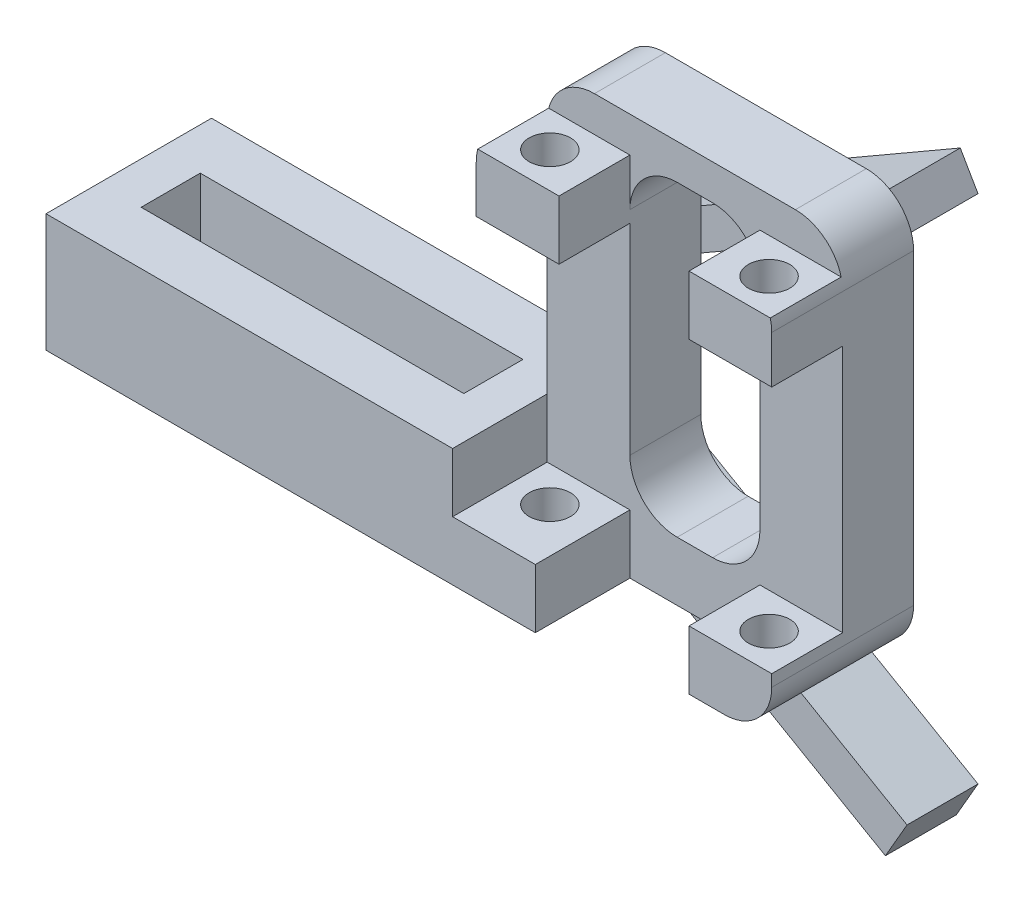
SolidWorks part; units mm, degrees
ref_plane "Alzado" through (0, 0, 0) normal (0, 0, 1) x (1, 0, 0)
ref_plane "Planta" through (0, 0, 0) normal (0, 1, 0) x (1, 0, 0)
ref_plane "Vista lateral" through (0, 0, 0) normal (1, 0, 0) x (0, 0, -1)
sketch "Croquis1" plane through (0, 0, 0) normal (0, 0, 1) x (1, 0, 0)
  line L1 (0, 0) -> (-25, 0)
  line L2 (0, 0) -> (0, -34)
  line L3 (0, -34) -> (-25, -34)
  line L4 (-25, 0) -> (-25, -34)
  dimension "D1" = 34
  dimension "D2" = 25
extrude "Saliente-Extruir1" add sketch "Croquis1" along normal blind 6
sketch "Croquis2" plane through (0, 0, 6) normal (0, 0, 1) x (1, 0, 0)
  line L0 (-25, 0) -> (-25, -34) construction
  line L1 (-25, -3) -> (-18, -3)
  line L2 (-25, -3) -> (-25, -8)
  line L3 (-25, -8) -> (-18, -8)
  line L4 (-18, -3) -> (-18, -8)
  line L5 (-12.5, 0) -> (-12.5, -3.7479) construction
  line L6 (0, 0) -> (-25, 0) construction
  line L7 (0, -8) -> (-7, -8)
  line L8 (-25, -34) -> (0, -34) construction
  line L9 (0, -34) -> (0, -29)
  line L10 (-7, -3) -> (-7, -8)
  line L11 (-18, 0) -> (-18, -3) construction
  line L12 (0, -3) -> (-7, -3)
  line L13 (0, -3) -> (0, -8)
  line L14 (-25, -29) -> (-18, -29)
  line L15 (-18, -34) -> (-18, -29)
  line L16 (-25, -34) -> (-18, -34)
  line L17 (-25, -34) -> (-25, -29)
  line L18 (0, -34) -> (-7, -34)
  line L19 (-7, -34) -> (-7, -29)
  line L20 (0, -29) -> (-7, -29)
  dimension "D1" = 5
  dimension "D2" = 3
  dimension "D3" = 7
  dimension "D4" = 7
  dimension "D5" = 5
extrude "Saliente-Extruir2" add sketch "Croquis2" along normal blind 6
sketch "Croquis3" plane through (0, 0, 6) normal (0, 0, 1) x (1, 0, 0)
  line L1 (-18, -3) -> (-7, -3)
  line L2 (-18, -3) -> (-18, -29)
  line L3 (-18, -29) -> (-7, -29)
  line L4 (-7, -3) -> (-7, -29)
extrude "Cortar-Extruir1" cut sketch "Croquis3" against normal up to next
fillet "Redondeo1" radius 4 8 edges at (-18, -29, 3) (-7, -29, 3) (-7, -3, 3) (-18, -3, 3) (0, 0, 3) (0, -34, 6) (-25, -34, 6) (-25, 0, 3)
sketch "Croquis5" plane through (0, 0, 0) normal (0, 0, -1) x (-1, 0, 0)
  line L0 (25, -29) -> (25, -30)
  line L1 (25, -34) -> (25, -36.4781) construction
  line L2 (25, -34) -> (59.4, -34)
  line L6 (25, -36.4781) -> (59.4, -36.4781) construction
  line L7 (25, -34) -> (21, -34)
  line L8 (25, -29) -> (25, -24)
  line L9 (25, -4) -> (25, -30) construction
  line L10 (25, -24) -> (59.4, -24)
  line L11 (59.4, -24) -> (59.4, -34)
  arc A1 (21, -34) -> (25, -30) centre (21, -30) ccw construction
  arc A2 (21, -34) -> (25, -30) centre (21, -30) ccw
  dimension "D1" = 34.4
  dimension "D2" = 10
extrude "Saliente-Extruir3" add sketch "Croquis5" against normal blind 12
sketch "Croquis6" plane through (0, 0, 12) normal (0, 0, 1) x (1, 0, 0)
  line L4 (-25, -29) -> (-25, -24)
  line L6 (-18, -29) -> (-25, -29)
  line L10 (-59.4, -34) -> (-18, -34)
  line L11 (-18, -34) -> (-18, -29)
  line L12 (-18, -29) -> (-25, -29)
  line L16 (-59.4, -34) -> (-18, -34)
  line L17 (-18, -34) -> (-18, -29)
  line L20 (-25, -29) -> (-25, -24)
  line L22 (-25, -24) -> (-59.4, -24)
  line L23 (-25, -24) -> (-59.4, -24)
  line L24 (-59.4, -24) -> (-59.4, -34)
  line L25 (-59.4, -24) -> (-59.4, -34)
  dimension "D1" = 0
extrude "Saliente-Extruir4" add sketch "Croquis6" along normal blind 2
sketch "Croquis7" plane through (0, -3, 0) normal (0, 1, 0) x (1, 0, 0)
  line L0 (-18, -12) -> (-18, -6) construction
  line L2 (-18, -6) -> (-7, -6) construction
  line L3 (-24.873, -6) -> (-24.873, -12) construction
  line L4 (-12.5, -8.2225) -> (-12.5, -6) construction
  circle A0 centre (-21.773, -9) radius 1.75
  circle A1 centre (-3.227, -9) radius 1.75
  point P4 (-18, -9)
  dimension "D1" = 3.5
  dimension "D2" = 3.1
extrude "Cortar-Extruir2" cut sketch "Croquis7" against normal up to surface (31 mm away) up to face at (-22.1, -34, 8)
sketch "Croquis8" plane through (0, -24, 0) normal (0, 1, 0) x (1, 0, 0)
  line L0 (-59.4, -14) -> (-59.4, 0) construction
  line L2 (-59.4, 0) -> (-25, 0) construction
  line L3 (-55.85, -8.1609) -> (-59.4, -8.1609) construction
  line L11 (-28.55, -4.5) -> (-55.85, -4.5)
  line L12 (-28.55, -4.5) -> (-28.55, -9.5)
  line L13 (-28.55, -9.5) -> (-55.85, -9.5)
  line L14 (-55.85, -4.5) -> (-55.85, -9.5)
  point P2 (-59.4, -7)
  point P3 (-55.85, -7)
  point P7 (-42.2, 0)
  point P8 (-42.2, -4.5)
  dimension "D1" = 5
  dimension "D2" = 27.3
extrude "Cortar-Extruir3" cut sketch "Croquis8" against normal up to next
sketch "Croquis9" plane through (0, 0, 0) normal (0, 0, -1) x (-1, 0, 0)
  line L2 (0.5503, -3.1054) -> (23.5, -16.3554) construction
  line L3 (0.5503, -3.1054) -> (0.16, -2.88)
  line L4 (2.0503, -0.5073) -> (25, -13.7573)
  line L5 (25, -4) -> (25, -24) construction
  line L7 (0.5503, -3.1054) -> (6.6125, -6.6054)
  line L8 (6.6125, -6.6054) -> (17.4378, -12.8554)
  line L9 (17.4378, -12.8554) -> (23.5, -16.3554)
  line L10 (13.5252, -7.1323) -> (12.5327, -8.8513) construction
  line L11 (23.5, -16.3554) -> (25, -17.2214)
  line L12 (12.0252, -9.7304) -> (12.0252, -39.7304) construction
  line L13 (25.3336, -36.2813) -> (2.3839, -49.5313)
  line L14 (0.5503, -46.3554) -> (2.3839, -49.5313)
  line L15 (23.5, -16.3554) -> (25, -13.7573)
  line L16 (23.5, -33.1054) -> (25.3336, -36.2813)
  line L17 (0.5503, -3.1054) -> (2.0503, -0.5073)
  line L18 (23.5, -33.1054) -> (17.4378, -36.6054)
  line L19 (0, -8) -> (-5.0025, -8) construction
  line L20 (-5.0025, -8) -> (-5.0025, -29) construction
  line L21 (25, -24) -> (25, -45.2131) construction
  line L23 (0, -46.0728) -> (0, -29) construction
  line L24 (23.5, -33.1054) -> (25, -32.2394)
  line L25 (17.4378, -36.6054) -> (6.6125, -42.8554)
  line L26 (6.6125, -42.8554) -> (0.5503, -46.3554)
  line L27 (0.5503, -46.3554) -> (0.16, -46.5808) construction
  arc A1 (4, 0) -> (0, -4) centre (4, -4) ccw construction
  line M5 (18, -7) -> (18, -25)
  arc M10 (7, -7) -> (11, -3) centre (11, -7) cw
  line M15 (4, -34) -> (59.4, -34)
  dimension "D1" = 26.5
  dimension "D2" = 3
  dimension "D3" = 60
  dimension "D4" = 3
  dimension "D5" = 7
  dimension "D6" = 7
  dimension "D7" = 30
  dimension "D8" = 60
  dimension "D9" = 7
  dimension "D10" = 7
extrude "Saliente-Extruir5" add sketch "Croquis9" along normal blind 6 contours L9 L15 L4 M5 | L8 L9 L4 L7 M5 M10 | L17 L7 L4 M10 | L18 L25 L13 L16 M15 | L25 L26 L14 L13 M15 | L16 L18 M15 region at (-4.3748, -3.5927, 0) region at (-12.7222, -8.4353, 0) region at (-21.14, -13.1915, 0) region at (-12.8439, -41.3915, 0) region at (-23.1557, -33.7018, 0)
